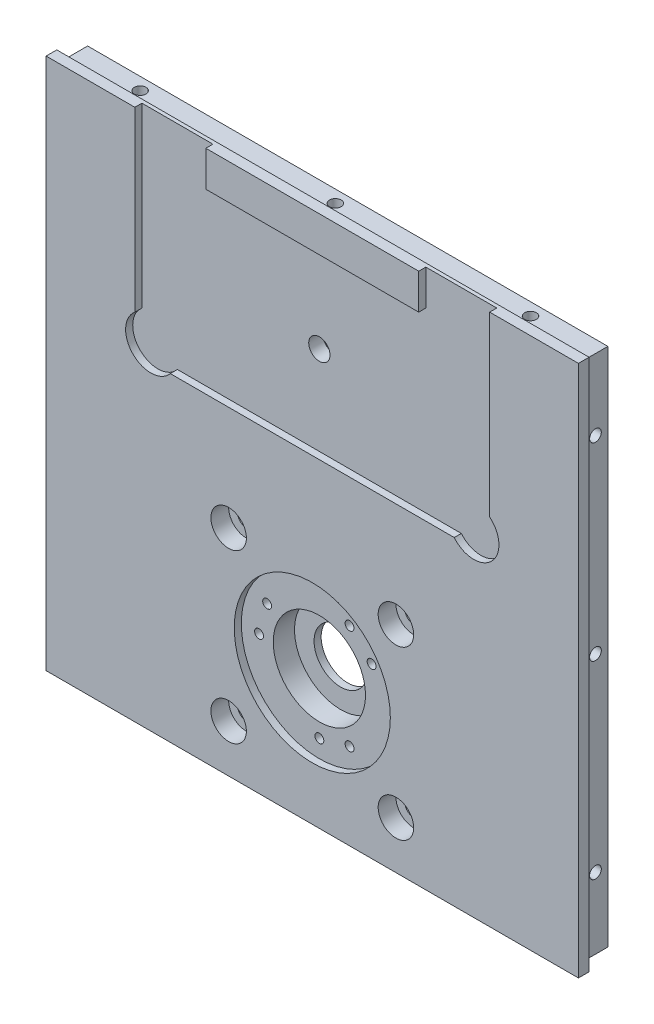
SolidWorks part; units mm, degrees
ref_plane "Спереди" through (0, 0, 0) normal (0, 0, 1) x (1, 0, 0)
ref_plane "Сверху" through (0, 0, 0) normal (0, 1, 0) x (1, 0, 0)
ref_plane "Справа" through (0, 0, 0) normal (1, 0, 0) x (0, 0, -1)
sketch "Эскиз1" plane through (0, 0, 0) normal (0, 0, 1) x (1, 0, 0)
  line L1 (0, 0) -> (150, 0)
  line L2 (0, 0) -> (0, 150)
  line L3 (0, 150) -> (150, 150)
  line L4 (150, 0) -> (150, 150)
  dimension "D1" = 150
  dimension "D2" = 150
extrude "Бобышка-Вытянуть1" add sketch "Эскиз1" along normal blind 10
sketch "Эскиз2" plane through (0, 0, 10) normal (0, 0, 1) x (1, 0, 0)
  line L0 (0, 0) -> (150, 0) construction
  circle A0 centre (75, 37) radius 13
  point P4 (75, 0)
  dimension "D3" = 26
  dimension "D1" = 0
  dimension "D2" = 37
extrude "Вырез-Вытянуть1" cut sketch "Эскиз2" against normal blind 8
sketch "Эскиз3" plane through (0, 0, 10) normal (0, 0, 1) x (1, 0, 0)
  circle A0 centre (75, 37) radius 7.5
  dimension "D1" = 15
extrude "Вырез-Вытянуть3" cut sketch "Эскиз3" against normal through all
sketch "Эскиз4" plane through (0, 0, 10) normal (0, 0, 1) x (1, 0, 0)
  circle A0 centre (75, 37) radius 22
  dimension "D1" = 44
extrude "Вырез-Вытянуть4" cut sketch "Эскиз4" against normal blind 2
sketch "Эскиз5" plane through (0, 0, 10) normal (0, 0, 1) x (1, 0, 0)
  circle A0 centre (51.43, 13.43) radius 2.5
  circle A1 centre (75, 37) radius 7.5 construction
  circle A2 centre (98.57, 13.43) radius 2.5
  circle A3 centre (98.57, 60.57) radius 2.5
  circle A4 centre (51.43, 60.57) radius 2.5
  dimension "D1" = 5
  dimension "D2" = 23.57
  dimension "D3" = 23.57
  dimension "D4" = 2
  dimension "D5" = 2
extrude "Вырез-Вытянуть5" cut sketch "Эскиз5" against normal through all
sketch "Эскиз6" plane through (0, 0, 0) normal (0, 0, -1) x (-1, 0, 0)
  line L0 (0, 150) -> (0, 0) construction
  line L1 (-148.3, 148.3) -> (-1.7, 148.3)
  line L2 (-148.3, 148.3) -> (-148.3, 1.7)
  line L3 (-148.3, 1.7) -> (-1.7, 1.7)
  line L4 (-1.7, 148.3) -> (-1.7, 1.7)
  line L5 (-150, 150) -> (0, 150) construction
  line L6 (-150, 0) -> (-150, 150) construction
  line L7 (0, 0) -> (-150, 0) construction
  line L9 (-159.0813, 154.0692) -> (4.376, 154.0692)
  line L10 (-159.0813, 154.0692) -> (-159.0813, -3.2509)
  line L11 (-159.0813, -3.2509) -> (4.376, -3.2509)
  line L12 (4.376, 154.0692) -> (4.376, -3.2509)
  dimension "D1" = 1.7
  dimension "D2" = 1.7
  dimension "D3" = 1.7
  dimension "D4" = 1.7
extrude "Вырез-Вытянуть6" cut sketch "Эскиз6" against normal blind 7
sketch "Эскиз7" plane through (0, 1.7, 0) normal (0, -1, 0) x (1, 0, 0)
  line L1 (0, 10) -> (0, 7) construction
  line L2 (148.3, 7) -> (1.7, 7) construction
  circle A0 centre (20, 3.5) radius 1.65
  circle A1 centre (75, 3.5) radius 1.65
  circle A2 centre (130, 3.5) radius 1.65
  dimension "D4" = 3.3
  dimension "D1" = 3.5
  dimension "D2" = 20
  dimension "D3" = 3
extrude "Вырез-Вытянуть7" cut sketch "Эскиз7" against normal blind 15
sketch "Эскиз8" plane through (0, 148.3, 0) normal (0, 1, 0) x (1, 0, 0)
  circle A0 centre (20, -3.5) radius 1.65
  circle A1 centre (75, -3.5) radius 1.65
  circle A2 centre (130, -3.5) radius 1.65
  circle A3 centre (20, -3.5) radius 1.65 construction
extrude "Вырез-Вытянуть8" cut sketch "Эскиз8" against normal blind 15
sketch "Эскиз9" plane through (148.3, 0, 0) normal (1, 0, 0) x (0, 0, -1)
  line L0 (0, 148.3) -> (0, 1.7) construction
  line L1 (-7, 1.7) -> (0, 1.7) construction
  line L2 (-7, 148.3) -> (0, 148.3) construction
  line L3 (-7, 148.3) -> (-7, 1.7) construction
  circle A0 centre (-3.5, 21.7) radius 1.65
  circle A1 centre (-3.5, 128.3) radius 1.65
  circle A2 centre (-3.5, 75) radius 1.65
  point P11 (0, 75)
  dimension "D1" = 3.3
  dimension "D2" = 3.5
  dimension "D3" = 20
  dimension "D4" = 20
  dimension "D5" = 0
extrude "Вырез-Вытянуть9" cut sketch "Эскиз9" against normal blind 15
sketch "Эскиз10" plane through (1.7, 0, 0) normal (-1, 0, 0) x (0, 0, 1)
  circle A0 centre (3.5, 128.3) radius 1.65
  circle A1 centre (3.5, 75) radius 1.65
  circle A2 centre (3.5, 21.7) radius 1.65
  circle A3 centre (3.5, 128.3) radius 1.65 construction
extrude "Вырез-Вытянуть10" cut sketch "Эскиз10" against normal blind 15
sketch "Эскиз12" plane through (0, 0, 10) normal (0, 0, 1) x (1, 0, 0)
  line L0 (75, 37) -> (89.7224, 45.5) construction
  line L1 (75, 37) -> (83.5, 22.2776) construction
  circle A0 centre (75, 20) radius 1.25
  circle A1 centre (75, 37) radius 7.5 construction
  circle A2 centre (60.2776, 45.5) radius 1.25
  circle A3 centre (89.7224, 45.5) radius 1.25
  circle A7 centre (58, 37) radius 1.25
  circle A8 centre (83.5, 22.2776) radius 1.25
  circle A9 centre (83.5, 51.7224) radius 1.25
  point P10 (75, 37)
  dimension "D1" = 2.5
  dimension "D2" = 0
  dimension "D3" = 17
  dimension "D6" = 90
  dimension "D4" = 3
  dimension "D5" = 2
extrude "Вырез-Вытянуть11" cut sketch "Эскиз12" against normal through all
sketch "Эскиз14" plane through (0, 0, 10) normal (0, 0, 1) x (1, 0, 0)
  circle A0 centre (51.43, 13.43) radius 5
  circle A1 centre (98.57, 13.43) radius 5
  circle A2 centre (98.57, 60.57) radius 5
  circle A3 centre (51.43, 60.57) radius 5
  dimension "D1" = 10
  dimension "D2" = 2
  dimension "D3" = 2
extrude "Вырез-Вытянуть12" cut sketch "Эскиз14" against normal blind 5
sketch "Эскиз15" plane through (0, 0, 10) normal (0, 0, 1) x (1, 0, 0)
  line L0 (150, 150) -> (0, 150) construction
  line L1 (25, 140) -> (125, 140)
  line L2 (25, 140) -> (25, 90)
  line L3 (25, 90) -> (125, 90)
  line L4 (125, 140) -> (125, 90)
  point P4 (75, 140)
  point P7 (75, 150)
  dimension "D1" = 0
  dimension "D2" = 10
  dimension "D3" = 50
  dimension "D4" = 100
extrude "Вырез-Вытянуть13" cut sketch "Эскиз15" against normal blind 2
sketch "Эскиз16" plane through (0, 0, 10) normal (0, 0, 1) x (1, 0, 0)
  line L0 (25, 90) -> (125, 90) construction
  line L1 (25, 140) -> (25, 90) construction
  circle A0 centre (29.5, 94.5) radius 7.1
  circle A1 centre (120.5, 94.5) radius 7.1
  circle A4 centre (120.5, 135.5) radius 7.1 [skipped]
  circle A5 centre (29.5, 135.5) radius 7.1 [skipped]
  dimension "D1" = 14.2
  dimension "D2" = 4.5
  dimension "D3" = 4.5
  dimension "D4" = 2
  dimension "D5" = 2
extrude "Вырез-Вытянуть14" cut sketch "Эскиз16" against normal up to surface (2 mm away) up to face at (75, 115, 8)
sketch "Эскиз17" plane through (0, 0, 10) normal (0, 0, 1) x (1, 0, 0)
  line L0 (34.9918, 90) -> (115.0082, 90) construction
  line L1 (25, 140) -> (25, 99.9918) construction
  circle A0 centre (75, 115) radius 3
  dimension "D1" = 6
  dimension "D2" = 25
  dimension "D3" = 50
extrude "Вырез-Вытянуть15" cut sketch "Эскиз17" against normal through all
sketch "Эскиз18" plane through (0, 0, 10) normal (0, 0, 1) x (1, 0, 0)
  line L0 (150, 150) -> (0, 150) construction
  line L1 (25, 140) -> (45, 140)
  line L2 (25, 140) -> (25, 150)
  line L3 (25, 150) -> (45, 150)
  line L4 (45, 140) -> (45, 150)
  line L6 (125, 140) -> (105, 140)
  line L7 (125, 140) -> (125, 150)
  line L8 (125, 150) -> (105, 150)
  line L9 (105, 140) -> (105, 150)
  dimension "D1" = 20
extrude "Вырез-Вытянуть16" cut sketch "Эскиз18" against normal up to surface (2 mm away) up to face at (78, 115, 8)
sketch "Эскиз19" plane through (0, 0, 0) normal (0, 0, -1) x (-1, 0, 0)
  line L13 (-69.2265, 115) -> (-72.1132, 120)
  line L14 (-72.1132, 120) -> (-77.8868, 120)
  line L15 (-77.8868, 120) -> (-80.7735, 115)
  line L16 (-80.7735, 115) -> (-77.8868, 110)
  line L17 (-77.8868, 110) -> (-72.1132, 110)
  line L18 (-72.1132, 110) -> (-69.2265, 115)
  circle A0 centre (-75, 115) radius 5 construction
  dimension "D1" = 10
extrude "Вырез-Вытянуть17" cut sketch "Эскиз19" against normal blind 4
